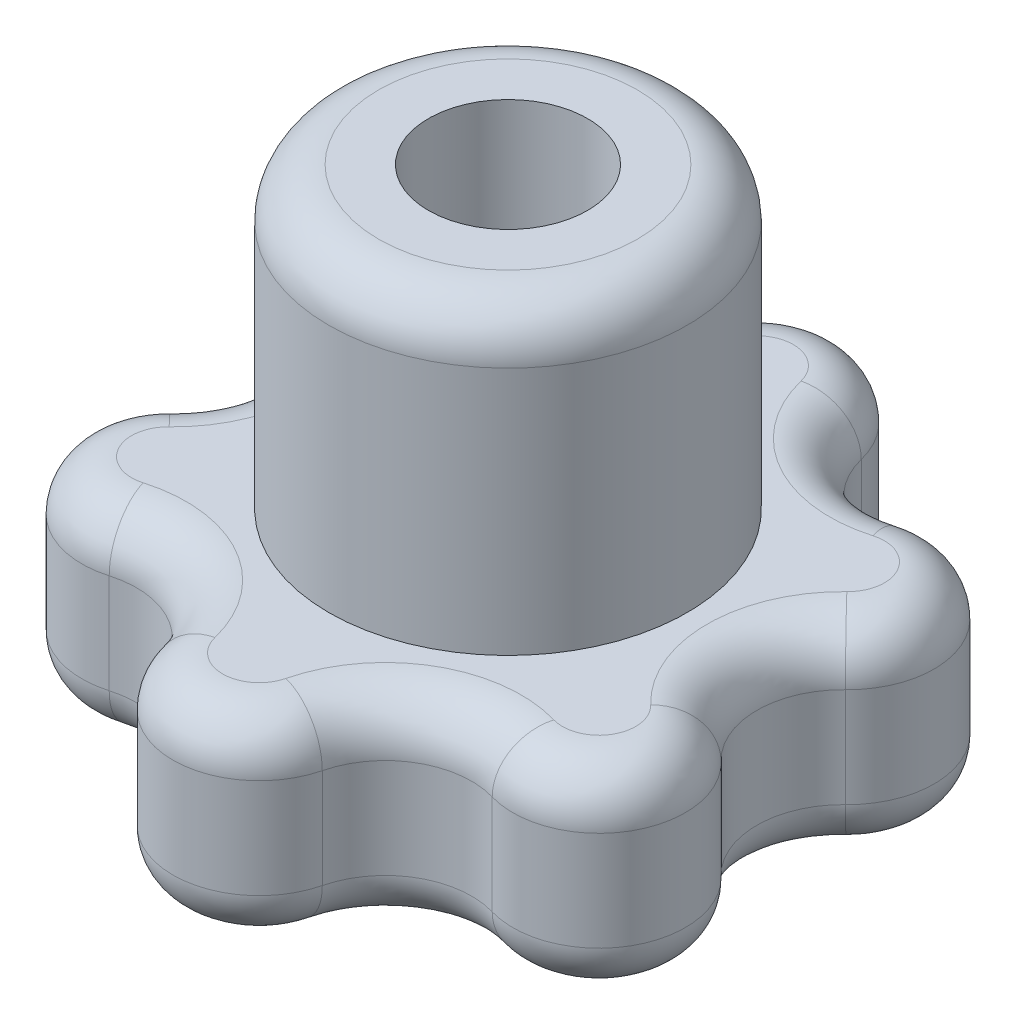
SolidWorks part; units mm, degrees
ref_plane "Спереди" through (0, 0, 0) normal (0, 0, 1) x (1, 0, 0)
ref_plane "Сверху" through (0, 0, 0) normal (0, 1, 0) x (1, 0, 0)
ref_plane "Справа" through (0, 0, 0) normal (1, 0, 0) x (0, 0, -1)
sketch "Эскиз1" plane through (0, 0, 0) normal (0, 1, 0) x (1, 0, 0)
  line L1 (0, 3.3486) -> (-2.9, 1.6743)
  line L2 (-2.9, 1.6743) -> (-2.9, -1.6743)
  line L3 (-2.9, -1.6743) -> (0, -3.3486)
  line L4 (0, -3.3486) -> (2.9, -1.6743)
  line L5 (2.9, -1.6743) -> (2.9, 1.6743)
  line L6 (2.9, 1.6743) -> (0, 3.3486)
  circle A0 centre (0, 0) radius 5 construction
  arc A1 (1.6835, 5.416) -> (-1.6835, 5.416) centre (0, 5) ccw
  arc A2 (1.6835, 5.416) -> (3.8486, 4.166) centre (3.3671, 5.832) ccw
  arc A3 (-1.6835, -5.416) -> (1.6835, -5.416) centre (0, -5) ccw
  arc A4 (3.8486, -4.166) -> (1.6835, -5.416) centre (3.3671, -5.832) ccw
  arc A5 (5.5322, 1.25) -> (3.8486, 4.166) centre (4.3301, 2.5) ccw
  arc A6 (5.5322, 1.25) -> (5.5322, -1.25) centre (6.7342, 0) ccw
  arc A7 (3.8486, -4.166) -> (5.5322, -1.25) centre (4.3301, -2.5) ccw
  arc A8 (-3.8486, 4.166) -> (-1.6835, 5.416) centre (-3.3671, 5.832) ccw
  arc A9 (-3.8486, 4.166) -> (-5.5322, 1.25) centre (-4.3301, 2.5) ccw
  arc A10 (-5.5322, -1.25) -> (-5.5322, 1.25) centre (-6.7342, 0) ccw
  arc A11 (-1.6835, -5.416) -> (-3.8486, -4.166) centre (-3.3671, -5.832) ccw
  arc A12 (-5.5322, -1.25) -> (-3.8486, -4.166) centre (-4.3301, -2.5) ccw
  circle A13 centre (0, 0) radius 2.9 construction
  dimension "D1" = 10
extrude "Бобышка-Вытянуть1" add sketch "Эскиз1" along normal blind 4 contours A7 A6 A5 A2 A1 A8 A9 A10 A12 A11 A3 A4
sketch "Эскиз2" plane through (0, 4, 0) normal (0, 1, 0) x (1, 0, 0)
  circle A0 centre (0, 0) radius 3.6
  dimension "D1" = 7.2
extrude "Бобышка-Вытянуть2" add sketch "Эскиз2" along normal blind 6
sketch "Эскиз3" plane through (0, 10, 0) normal (0, 1, 0) x (1, 0, 0)
  circle A0 centre (0, 0) radius 1.6
  dimension "D1" = 3.2
extrude "Вырез-Вытянуть1" cut sketch "Эскиз3" against normal through all
extrude "Вырез-Вытянуть2" cut sketch "Эскиз1<3>" along normal blind 2.5 contours L1 L2 L3 L4 L5 L6
sketch "Эскиз1<3>" plane through (0, 0, 0) normal (0, 1, 0) x (1, 0, 0) same geometry as "Эскиз1"
fillet "Скругление1" radius 1 25 edges at (-2.5, 4, 4.3301) (-5.832, 4, 3.3671) (-5, 4, 0) (-5.832, 4, -3.3671) (-2.5, 4, -4.3301) (0, 4, -6.7342) (2.5, 4, -4.3301) (5.832, 4, -3.3671) (5, 4, 0) (5.832, 4, 3.3671) (2.5, 4, 4.3301) (-2.5, 0, 4.3301) (-5.832, 0, 3.3671) (-5, 0, 0) (-5.832, 0, -3.3671) (-2.5, 0, -4.3301) (0, 0, -6.7342) (2.5, 0, -4.3301) (5.832, 0, -3.3671) (5, 0, 0) (5.832, 0, 3.3671) (2.5, 0, 4.3301) (0, 10, 3.6) (0, 4, 6.7342) (0, 0, 6.7342)
